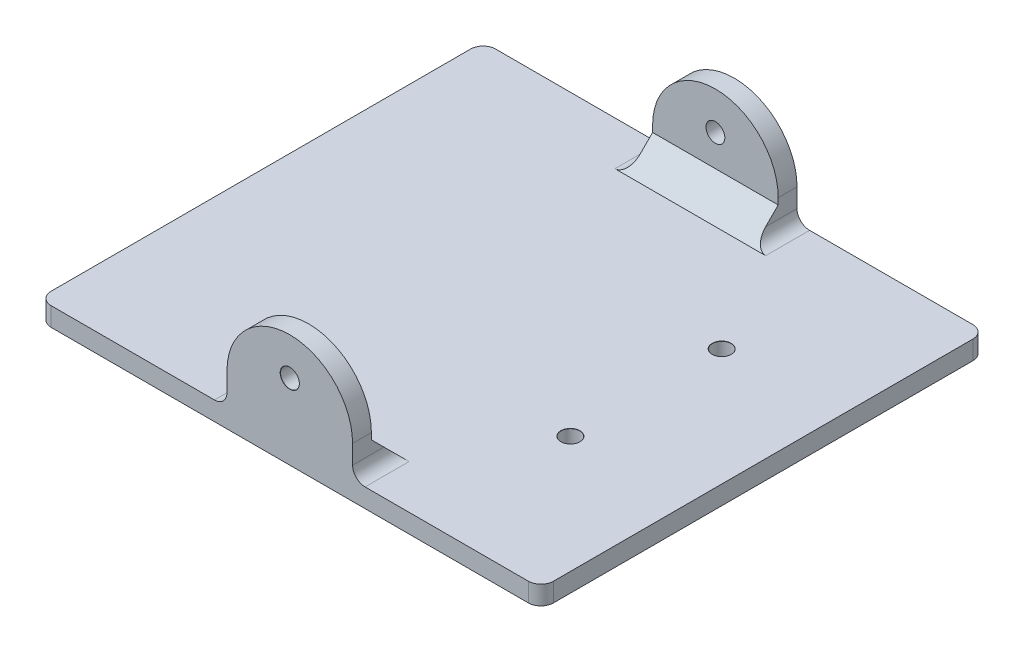
SolidWorks part; units mm, degrees
material "ABS"
ref_plane "Front Plane" through (0, 0, 0) normal (0, 0, 1) x (1, 0, 0)
ref_plane "Top Plane" through (0, 0, 0) normal (0, 1, 0) x (1, 0, 0)
ref_plane "Right Plane" through (0, 0, 0) normal (1, 0, 0) x (0, 0, -1)
sketch "Sketch1" plane through (0, 0, 0) normal (0, 1, 0) x (1, 0, 0)
  line L1 (-40, -35.395) -> (40, -35.395)
  line L2 (-40, -35.395) -> (-40, 35.395)
  line L3 (-40, 35.395) -> (40, 35.395)
  line L4 (40, -35.395) -> (40, 35.395)
  line L5 (-40, -35.395) -> (40, 35.395) construction
  line L6 (-40, 35.395) -> (40, -35.395) construction
  point P0 (0, 0)
  dimension "D1" = 80
  dimension "D2" = 70.79
extrude "Boss-Extrude1" add sketch "Sketch1" along normal blind 3
sketch "Sketch2" plane through (0, 3, 0) normal (0, 1, 0) x (1, 0, 0)
  line L0 (0, 10.8925) -> (0, -11.0937) construction
  line L1 (-10, 35.395) -> (10, 35.395)
  line L2 (-10, 35.395) -> (-10, 32.395)
  line L3 (-10, 32.395) -> (10, 32.395)
  line L4 (10, 35.395) -> (10, 32.395)
  line L5 (-10, -35.395) -> (10, -35.395)
  line L6 (-10, -35.395) -> (-10, -32.395)
  line L7 (-10, -32.395) -> (10, -32.395)
  line L8 (10, -35.395) -> (10, -32.395)
  line L9 (40, 35.395) -> (-40, 35.395) construction
  line L10 (-40, -35.395) -> (40, -35.395) construction
  dimension "D1" = 3
  dimension "D2" = 20
hole_wizard "Ø3.0mm Dowel Hole2" positions "Sketch7" profile "Sketch8" hole size "Ø3.0" standard "ANSI Metric" end condition through all
sketch "Sketch7" plane through (0, 3, 0) normal (0, 1, 0) x (1, 0, 0)
  point P0 (21.35, 12.05)
  point P3 (21.35, -12.05)
sketch "Sketch8" plane through (21.35, 3, -12.05) normal (1, 0, 0) x (0, 0, 1)
  line L0 (0, 0) -> (0, 3)
  line L1 (0, 3) -> (1.5, 3)
  line L2 (1.5, 3) -> (1.5, 0.025)
  line L3 (1.5, 0.025) -> (1.525, 0)
  line L5 (1.525, 0) -> (0, 0)
  line L6 (-1.5, 0.025) -> (-1.525, 0) construction
  line L11 (0, -6.35) -> (0, 107.95) construction
  dimension "Thru Hole Dia." = 3
  dimension "Thru Hole Depth" = 3
  dimension "Near C'Sink Dia." = 3.05
  dimension "Near C'Sink Angle" = 90
extrude "Boss-Extrude2" add sketch "Sketch2" along normal blind 15
hole_wizard "Ø3.0mm Dowel Hole3" positions "Sketch9" profile "Sketch10" hole size "Ø3.0" standard "ANSI Metric" end condition through all
sketch "Sketch9" plane through (0, 0, 35.395) normal (0, 0, 1) x (1, 0, 0)
  point P0 (0, 12)
  dimension "D1" = 12
sketch "Sketch10" plane through (0, 12, 35.395) normal (1, 0, 0) x (0, -1, 0)
  line L0 (0, 0) -> (0, 70.79)
  line L1 (0, 70.79) -> (1.5, 70.79)
  line L2 (1.5, 70.79) -> (1.5, 0.025)
  line L3 (1.5, 0.025) -> (1.525, 0)
  line L5 (1.525, 0) -> (0, 0)
  line L6 (-1.5, 0.025) -> (-1.525, 0) construction
  line L11 (0, -6.35) -> (0, 107.95) construction
  dimension "Thru Hole Dia." = 3
  dimension "Thru Hole Depth" = 70.79
  dimension "Near C'Sink Dia." = 3.05
  dimension "Near C'Sink Angle" = 90
fillet "Fillet1" 2 edges at (10, 18, 33.895) (-10, 18, 33.895) type full round first side face at (10, 10.5, 33.895) second side face at (-10, 10.5, 33.895) middle face at (0, 18, 33.895)
fillet "Fillet2" 2 edges at (10, 18, -33.895) (-10, 18, -33.895) type full round first side face at (10, 10.5, -33.895) second side face at (-10, 10.5, -33.895) middle face at (0, 18, -33.895)
fillet "Fillet3" radius 2 4 edges at (-10, 3, 33.895) (-10, 3, -33.895) (10, 3, -33.895) (10, 3, 33.895)
fillet "Fillet4" radius 2 4 edges at (40, 1.5, -35.395) (40, 1.5, 35.395) (-40, 1.5, 35.395) (-40, 1.5, -35.395)
chamfer "Chamfer1" distance 4 angle 45 2 edges at (0, 3, -32.395) (0, 3, 32.395)
